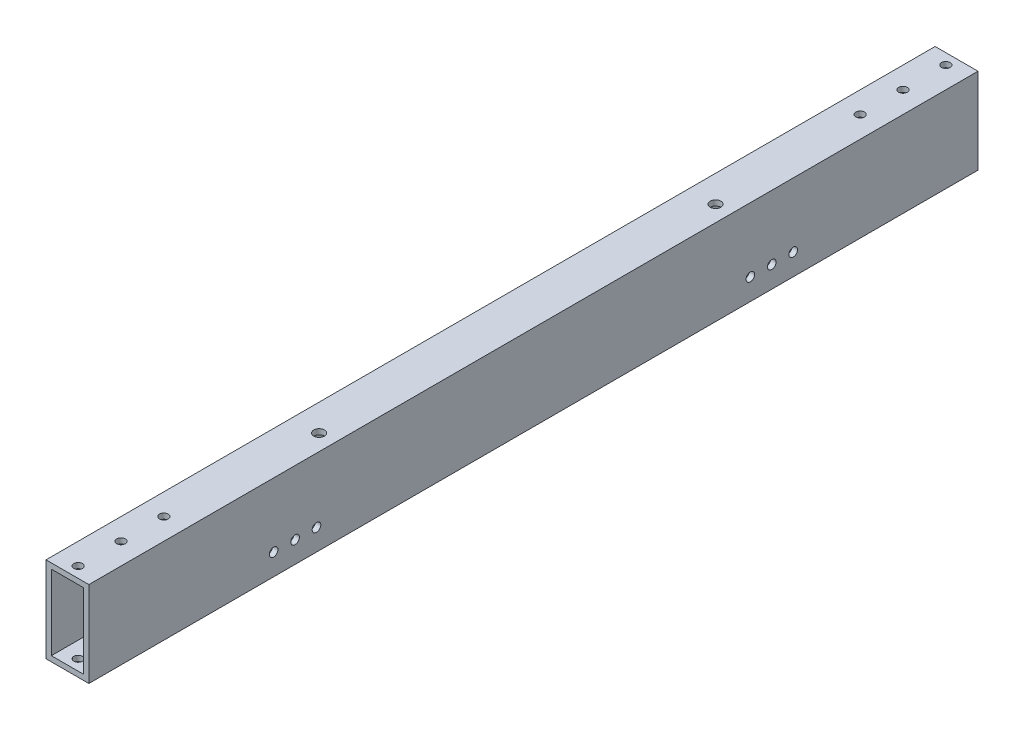
SolidWorks part; units mm, degrees
material "6061-T6 (SS)"
ref_plane "Front" through (0, 0, 0) normal (0, 0, 1) x (1, 0, 0)
ref_plane "Top" through (0, 0, 0) normal (0, 1, 0) x (1, 0, 0)
ref_plane "Right" through (0, 0, 0) normal (1, 0, 0) x (0, 0, -1)
sketch "Sketch1" plane through (0, 0, 0) normal (0, 0, 1) x (1, 0, 0)
  line L1 (-12.7, -25.4) -> (12.7, -25.4)
  line L2 (-12.7, -25.4) -> (-12.7, 25.4)
  line L3 (-12.7, 25.4) -> (12.7, 25.4)
  line L4 (12.7, -25.4) -> (12.7, 25.4)
  line L5 (-12.7, -25.4) -> (12.7, 25.4) construction
  line L6 (-12.7, 25.4) -> (12.7, -25.4) construction
  point P0 (0, 0)
  dimension "D1" = 25.4
  dimension "D2" = 50.8
extrude "Extrude-Thin1" add sketch "Sketch1" along normal blind 527.05 thin thin type one direction reverse wall 3.175
hole_wizard "#10 Clearance Hole1" positions "Sketch2" profile "Sketch3" hole size "#10" standard "ANSI Inch" end condition through all
sketch "Sketch2" plane through (0, 25.4, 0) normal (0, 1, 0) x (1, 0, 0)
  line L0 (12.7, -527.05) -> (-12.7, -527.05) construction
  line L1 (-12.7, -527.05) -> (-12.7, 0) construction
  point P0 (0, -520.7)
  point P2 (0, -495.3)
  point P4 (0, -469.9)
  point P6 (0, -6.35)
  point P8 (0, -31.75)
  point P10 (0, -57.15)
  dimension "D1" = 6.35
  dimension "D2" = 12.7
  dimension "D3" = 25.4
  dimension "D4" = 25.4
  dimension "D5" = 6.35
  dimension "D6" = 25.4
  dimension "D7" = 25.4
sketch "Sketch3" plane through (0, 25.4, 520.7) normal (1, 0, 0) x (0, 0, 1)
  line L0 (0, 0) -> (0, 50.8)
  line L1 (0, 50.8) -> (2.5527, 50.8)
  line L2 (2.5527, 50.8) -> (2.5527, 0)
  line L5 (2.5527, 0) -> (0, 0)
  line L11 (0, -6.35) -> (0, 107.95) construction
  dimension "Thru Hole Dia." = 5.1054
  dimension "Thru Hole Depth" = 50.8
sketch "Sketch6" plane through (0, -25.4, 0) normal (0, -1, 0) x (-1, 0, 0)
  point P0 (3.175, -70.358)
  point P3 (-3.175, -95.758)
  point P6 (3.175, -121.158)
  point P9 (-3.175, -146.558)
  point P12 (3.175, -171.958)
  point P15 (-3.175, -197.358)
  point P22 (-3.175, -248.158)
  point P25 (3.175, -273.558)
  point P28 (-3.175, -298.958)
  point P31 (3.175, -324.358)
  point P34 (-3.175, -349.758)
  point P37 (3.175, -375.158)
  point P40 (-3.175, -400.558)
  point P43 (3.175, -425.958)
  point P46 (-3.175, -451.358)
  point P54 (3.175, -222.758)
hole_wizard "1/8 (0.13) Diameter Hole1" positions "Sketch6" profile "Sketch5" hole size "1/8" standard "ANSI Inch" end condition up to next
sketch "Sketch5" plane through (-3.175, -25.4, 70.358) normal (1, 0, 0) x (0, 0, -1)
  line L0 (0, 0) -> (0, 3.175)
  line L1 (0, 3.175) -> (1.651, 3.175)
  line L2 (1.651, 3.175) -> (1.651, 0)
  line L5 (1.651, 0) -> (0, 0)
  line L11 (0, -6.35) -> (0, 107.95) construction
  dimension "Thru Hole Dia." = 3.302
  dimension "Thru Hole Depth" = 3.175
sketch "Sketch9" plane through (0, 25.4, 0) normal (0, 1, 0) x (1, 0, 0)
  line L0 (12.7, 0) -> (-12.7, 0) construction
  line L1 (12.7, -527.05) -> (12.7, 0) construction
  line L2 (12.7, -527.05) -> (-12.7, -527.05) construction
  point P0 (3.175, -146.05)
  point P2 (3.175, -381)
  dimension "D1" = 146.05
  dimension "D2" = 9.525
  dimension "D3" = 146.05
hole_wizard "1/4 (0.25) Diameter Hole1" positions "Sketch9" profile "Sketch8" hole size "1/4" standard "ANSI Inch"
sketch "Sketch8" plane through (3.175, 25.4, 146.05) normal (1, 0, 0) x (0, 0, 1)
  line L0 (0, 0) -> (0, 12.6265)
  line L1 (0, 12.6265) -> (3.175, 10.7188)
  line L2 (3.175, 10.7188) -> (3.175, 0)
  line L5 (3.175, 0) -> (0, 0)
  line L10 (0, 12.6265) -> (-3.175, 10.7188) construction
  line L11 (0, -6.35) -> (0, 107.95) construction
  dimension "Hole Dia." = 6.35
  dimension "Hole Depth" = 10.7188
  dimension "Drill Angle" = 118
sketch "Sketch12" plane through (-12.7, 0, 0) normal (-1, 0, 0) x (0, 0, 1)
  point P44 (109.5375, -12.7)
  point P47 (122.2375, -12.7)
  point P50 (134.9375, -12.7)
  point P53 (392.1125, -12.7)
  point P56 (404.8125, -12.7)
  point P59 (417.5125, -12.7)
hole_wizard "CBORE for #10 Socket Head Cap Screw1" positions "Sketch12" profile "Sketch11" counterbore size "#10" standard "ANSI Inch" end condition through all
sketch "Sketch11" plane through (-12.7, -12.7, 109.5375) normal (0, 1, 0) x (0, 0, 1)
  line L0 (0, 0) -> (0, 25.4)
  line L1 (0, 25.4) -> (2.5527, 25.4)
  line L3 (2.5527, 25.4) -> (2.5527, 8.001)
  line L4 (2.5527, 8.001) -> (4.7625, 8.001)
  line L5 (4.7625, 8.001) -> (4.7625, 0)
  line L7 (4.7625, 0) -> (0, 0)
  line L11 (0, -6.35) -> (0, 107.95) construction
  dimension "Thru Hole Dia." = 5.1054
  dimension "Thru Hole Depth" = 25.4
  dimension "C'Bore Dia." = 9.525
  dimension "C'Bore Depth" = 8.001
